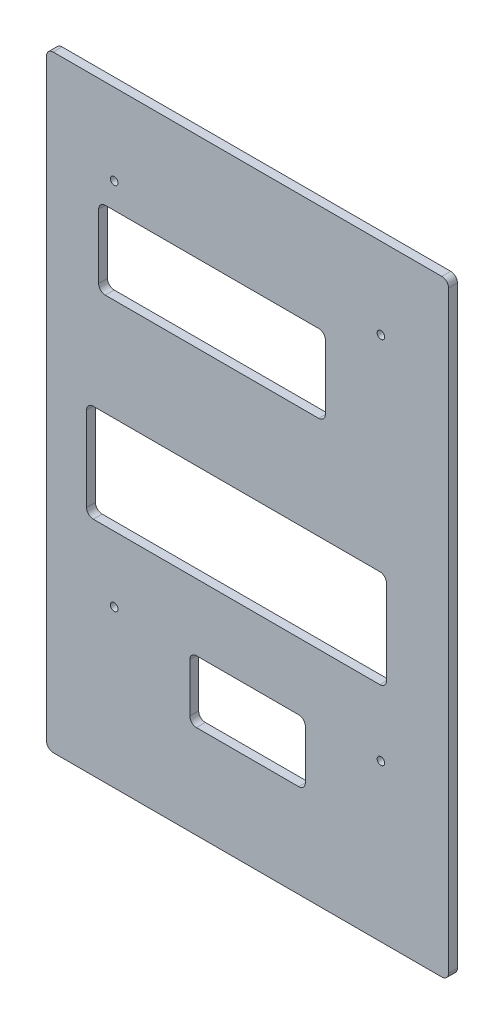
SolidWorks part; units mm, degrees
material "Verre"
ref_plane "Plan de face" through (0, 0, 0) normal (0, 0, 1) x (1, 0, 0)
ref_plane "Plan de dessus" through (0, 0, 0) normal (0, 1, 0) x (1, 0, 0)
ref_plane "Plan de droite" through (0, 0, 0) normal (1, 0, 0) x (0, 0, -1)
sketch "Esquisse1" plane through (0, 0, 0) normal (0, 0, 1) x (1, 0, 0)
  line L1 (0, 0) -> (180.86, 0)
  line L2 (0, 0) -> (0, 273)
  line L3 (0, 273) -> (180.86, 273)
  line L4 (180.86, 0) -> (180.86, 273)
  line L5 (64.43, 70) -> (116.43, 70)
  line L6 (64.43, 70) -> (64.43, 42)
  line L7 (64.43, 42) -> (116.43, 42)
  line L8 (116.43, 70) -> (116.43, 42)
  line L9 (18, 144) -> (152.93, 144)
  line L10 (18, 144) -> (18, 100)
  line L11 (18, 100) -> (152.93, 100)
  line L12 (152.93, 144) -> (152.93, 100)
  line L13 (23.43, 225) -> (125.43, 225)
  line L14 (23.43, 225) -> (23.43, 190)
  line L15 (23.43, 190) -> (125.43, 190)
  line L16 (125.43, 225) -> (125.43, 190)
  circle A0 centre (30.43, 236.5) radius 1.5
  circle A1 centre (150.43, 236.5) radius 1.5
  circle A2 centre (30.43, 70.5) radius 1.5
  circle A3 centre (150.43, 70.5) radius 1.5
  dimension "D5" = 3
  dimension "D8" = 3
  dimension "D13" = 3
  dimension "D14" = 3
  dimension "D1" = 180.86
  dimension "D2" = 273
  dimension "D3" = 30.43
  dimension "D4" = 36.5
  dimension "D6" = 36.5
  dimension "D7" = 30.43
  dimension "D9" = 30.43
  dimension "D10" = 30.43
  dimension "D11" = 70.5
  dimension "D12" = 70.5
  dimension "D16" = 42
  dimension "D17" = 28
  dimension "D18" = 30
  dimension "D19" = 44
  dimension "D20" = 52
  dimension "D21" = 18
  dimension "D22" = 27.93
  dimension "D23" = 48
  dimension "D24" = 35
  dimension "D26" = 102
  dimension "D25" = 55.43
  dimension "D15" = 64.43
extrude "Boss.-Extru.1" add sketch "Esquisse1" along normal blind 4
hole_wizard "Dégagement M31" positions "Esquisse2" profile "Esquisse3" hole size "M3" standard "ISO" end condition through all
sketch "Esquisse2" plane through (0, 0, 4) normal (0, 0, 1) x (1, 0, 0)
  point P0 (30.43, 236.5)
  point P3 (150.43, 236.5)
  point P6 (150.43, 70.5)
  point P9 (30.43, 70.5)
sketch "Esquisse3" plane through (30.43, 236.5, 4) normal (1, 0, 0) x (0, -1, 0)
  line L0 (0, 0) -> (0, 4)
  line L1 (0, 4) -> (1.7, 4)
  line L2 (1.7, 4) -> (1.7, 0)
  line L5 (1.7, 0) -> (0, 0)
  line L11 (0, -6.35) -> (0, 107.95) construction
  dimension "Diamètre du perçage jusqu'au prochain" = 3.4
  dimension "Profondeur du perçage jusqu'au prochain" = 4
fillet "Congé1" radius 3 16 edges at (0, 0, 2) (180.86, 0, 2) (116.43, 42, 2) (64.43, 42, 2) (116.43, 70, 2) (64.43, 70, 2) (152.93, 100, 2) (18, 100, 2) (152.93, 144, 2) (18, 144, 2) (180.86, 273, 2) (0, 273, 2) (125.43, 190, 2) (125.43, 225, 2) (23.43, 225, 2) (23.43, 190, 2)
sketch "Esquisse4" [suppressed] plane through (0, 0, 4) normal (0, 0, 1) x (1, 0, 0)
  line L0 (27.93, 165) -> (162.86, 165) construction
  line L1 (58.43, 190) -> (154.43, 190) construction
  line L3 (27.93, 165) -> (27.93, 135.3531) construction
  line L4 (162.86, 165) -> (162.86, 135.3531) construction
  line L5 (27.93, 141) -> (27.93, 103) construction
  line L6 (162.86, 103) -> (162.86, 141) construction
  dimension "D1" = 25
sketch "Esquisse5" plane through (0, 0, 0) normal (0, 0, -1) x (-1, 0, 0)
  line L0 (-56.9089, 202.3439) -> (421.0911, 202.3439) construction
  line L1 (107.0911, 240.8566) -> (1241.0911, 240.8566) construction
  line L2 (-94.2833, 174.0347) -> (-91.1852, 174.0347)
  line L3 (-91.1852, 174.0347) -> (-91.1824, 166.7906)
  line L4 (-84.6968, 170.3369) -> (-88.3318, 166.2594)
  line L5 (-88.3318, 166.2594) -> (-84.4535, 160.0184)
  line L6 (-84.4535, 160.0184) -> (-87.9228, 160.0184)
  line L7 (-87.9228, 160.0184) -> (-90.4278, 164.3432)
  line L8 (-91.1824, 160.0184) -> (-94.2833, 160.0184)
  line L9 (-94.2833, 160.0184) -> (-94.2833, 174.0347)
  line L10 (-78.7925, 174.0347) -> (-75.6893, 174.0347)
  line L11 (-75.6893, 174.0347) -> (-75.6893, 169.1495)
  line L12 (-69.5264, 160.0184) -> (-72.6249, 160.0184)
  line L13 (-75.6943, 160.0184) -> (-78.7925, 160.0184)
  line L14 (-78.7925, 160.0184) -> (-78.7925, 174.0347)
  line L15 (-139.2569, 172.9353) -> (-137.1581, 172.9353)
  line L16 (-137.1581, 172.9353) -> (-137.1581, 170.4368)
  line L17 (-137.1581, 170.4368) -> (-133.6735, 170.4368)
  line L18 (-133.6735, 170.4368) -> (-133.6735, 168.1381)
  line L19 (-133.6735, 168.1381) -> (-137.1581, 168.1381)
  line L20 (-137.1581, 168.1381) -> (-137.1581, 162.8704)
  line L21 (-133.2794, 162.5414) -> (-133.2794, 160.2428)
  line L22 (-140.1754, 168.1381) -> (-141.7532, 168.1381)
  line L23 (-141.7532, 168.1381) -> (-141.7532, 170.3369)
  line L24 (-141.7532, 170.3369) -> (-140.0239, 170.3369)
  line L25 (-140.0239, 170.3369) -> (-139.2569, 172.9353)
  line L26 (-12.9312, 172.9353) -> (-10.9324, 172.8354)
  line L27 (-10.9324, 172.8354) -> (-10.8324, 170.4368)
  line L28 (-10.8324, 170.4368) -> (-7.4344, 170.4368)
  line L29 (-7.4344, 170.4368) -> (-7.4344, 168.1381)
  line L30 (-7.4344, 168.1381) -> (-10.9324, 168.1381)
  line L31 (-10.9324, 168.1381) -> (-10.8324, 162.5414)
  line L32 (-57.505, 164.5403) -> (-59.1422, 164.5403)
  line L33 (-7.0347, 162.4415) -> (-7.0347, 160.2428)
  line L34 (-13.8145, 168.2381) -> (-15.4406, 168.2381)
  line L35 (-15.4406, 168.2381) -> (-15.4406, 170.4368)
  line L36 (-15.4406, 170.4368) -> (-13.7165, 170.4368)
  line L37 (-13.7165, 170.4368) -> (-12.9312, 172.9353)
  line L38 (-174.2363, 172.8354) -> (-163.6381, 172.8354)
  line L39 (-163.6381, 172.8354) -> (-163.6381, 170.2335)
  line L40 (-163.6381, 170.2335) -> (-167.3327, 170.2335)
  line L41 (-167.3327, 170.2335) -> (-167.3327, 160.0184)
  line L42 (-167.3327, 160.0184) -> (-170.5222, 160.0184)
  line L43 (-170.5222, 160.0184) -> (-170.5703, 170.2335)
  line L44 (-170.5703, 170.2335) -> (-174.2363, 170.2335)
  line L45 (-174.2363, 170.2335) -> (-174.2363, 172.8354)
  line L46 (-47.2135, 160.0661) -> (-47.2135, 172.8354)
  line L47 (-27.5226, 172.1358) -> (-25.224, 172.0359)
  line L48 (-25.224, 172.0359) -> (-24.9241, 170.6367)
  line L49 (-22.8254, 171.1364) -> (-21.1497, 169.4374)
  line L50 (-21.6333, 167.3283) -> (-20.2269, 167.1387)
  line L51 (-20.2269, 167.1387) -> (-20.3269, 164.8401)
  line L52 (-20.3269, 164.8401) -> (-21.726, 164.5403)
  line L53 (-21.3263, 162.4415) -> (-22.9253, 160.8424)
  line L54 (-22.9253, 160.8424) -> (-24.1246, 161.642)
  line L55 (-25.0241, 161.2422) -> (-25.3239, 159.843)
  line L56 (-25.3239, 159.843) -> (-27.5226, 159.943)
  line L57 (-27.5226, 159.943) -> (-27.8224, 161.3421)
  line L58 (-29.9212, 160.9424) -> (-31.5203, 162.5414)
  line L59 (-31.5203, 162.5414) -> (-30.7207, 163.7407)
  line L60 (-31.1205, 164.6402) -> (-32.5197, 164.94)
  line L61 (-32.5197, 164.94) -> (-32.4197, 167.1387)
  line L62 (-32.4197, 167.1387) -> (-31.0206, 167.4386)
  line L63 (-30.7207, 168.338) -> (-31.5203, 169.5373)
  line L64 (-31.5203, 169.5373) -> (-29.9212, 171.0364)
  line L65 (-27.8224, 170.6367) -> (-27.5226, 172.1358)
  line L66 (-121.3674, 171.736) -> (-113.2722, 160.1428)
  line L67 (-113.2722, 160.1428) -> (-130.1622, 160.2428)
  line L68 (-130.1622, 160.2428) -> (-121.3674, 171.736)
  line L69 (-101.122, 160.0184) -> (-104.166, 160.0184)
  line L70 (-107.2724, 160.0184) -> (-110.3739, 160.0184)
  line L71 (-110.3739, 160.0184) -> (-110.3739, 170.4368)
  line L72 (-110.3739, 170.4368) -> (-107.471, 170.4368)
  line L73 (-107.2724, 169.1495) -> (-107.471, 169.1495)
  line L74 (-55.5361, 159.943) -> (-54.06, 159.943)
  line L75 (-53.0008, 162.1272) -> (-53.0008, 160.2428)
  line L76 (-57.4815, 166.5394) -> (-57.4815, 167.3283)
  line L77 (-59.7101, 167.0388) -> (-62.9094, 167.1387)
  line L78 (-157.7434, 170.3369) -> (-154.6917, 170.352)
  line L79 (-151.8049, 170.352) -> (-148.7513, 170.3369)
  line L80 (-148.7513, 170.3369) -> (-148.6473, 160.0184)
  line L81 (-148.6473, 160.0184) -> (-151.6216, 160.0184)
  line L82 (-151.6216, 160.0184) -> (-151.6216, 161.4269)
  line L83 (-122.8785, 167.7334) -> (-124.9653, 161.2422)
  line L84 (-124.9653, 161.2422) -> (-127.9635, 161.3421)
  line L85 (-127.9635, 161.3421) -> (-122.8785, 167.7334)
  line L86 (-121.2675, 169.4374) -> (-115.4709, 161.3421)
  line L87 (-115.4709, 161.3421) -> (-123.6661, 161.3421)
  line L88 (-123.6661, 161.3421) -> (-121.2675, 169.4374)
  line L89 (-44.0087, 167.9383) -> (-44.0087, 170.3369)
  line L90 (-44.0267, 165.4648) -> (-44.0267, 162.5414)
  line L91 (-44.0267, 162.5414) -> (-41.8105, 162.5414)
  line L92 (-41.8105, 165.4648) -> (-44.0267, 165.4648)
  line L93 (-22.0456, 168.2381) -> (-21.1497, 169.4374)
  line L94 (-22.0456, 168.2381) -> (-21.6333, 167.3283)
  line L95 (-25.0241, 161.2422) -> (-24.1246, 161.642)
  line L96 (-31.1205, 164.6402) -> (-30.7207, 163.7407)
  line L97 (-30.7207, 168.338) -> (-31.0206, 167.4386)
  line L98 (-60.0892, 163.7407) -> (-60.0892, 162.8704)
  line L99 (-57.505, 164.5403) -> (-57.505, 163.8272)
  line L100 (-154.6917, 170.352) -> (-154.6917, 164.3054)
  line L101 (-151.8049, 170.352) -> (-151.8049, 164.3054)
  line L102 (-107.471, 169.1495) -> (-107.471, 170.4368)
  line L103 (-101.122, 160.0184) -> (-101.122, 167.4386)
  line L104 (-104.166, 160.0184) -> (-104.166, 165.9507)
  line L105 (-107.2724, 160.0184) -> (-107.2724, 165.9507)
  line L106 (-84.6968, 170.3369) -> (-88.0776, 170.3369)
  line L107 (-88.0776, 170.3369) -> (-91.1824, 166.7906)
  line L108 (-91.1824, 160.0184) -> (-91.1824, 163.8272)
  line L109 (-91.1824, 163.8272) -> (-90.4278, 164.3432)
  line L110 (-75.6943, 160.0184) -> (-75.6943, 165.9507)
  line L111 (-72.6249, 160.0184) -> (-72.6249, 166.7906)
  line L112 (-69.5264, 160.0184) -> (-69.5264, 167.4386)
  line L113 (-54.4145, 167.0061) -> (-54.4145, 162.6507)
  line L114 (-47.2135, 172.8354) -> (-41.5192, 172.8354)
  line L115 (-47.2135, 160.0661) -> (-40.67, 160.0661)
  line L116 (-44.0087, 170.3369) -> (-42.1743, 170.3369)
  line L117 (-44.0087, 167.9383) -> (-42.0498, 167.9383)
  arc A0 (-59.1422, 164.5403) -> (-60.0892, 163.7407) centre (-59.1422, 163.5797) ccw
  circle A1 centre (-26.3868, 165.9832) radius 2.3707
  arc A2 (-41.8105, 162.5414) -> (-41.8105, 165.4648) centre (-41.8105, 164.0031) ccw
  spline S0 degree 3 poles (-75.6943, 165.9507) (-75.607, 166.6089) (-75.1986, 167.568) (-73.6088, 168.4964) (-72.5255, 167.5211) (-72.6249, 166.7906) knots 0 0 0 0 0.394541 0.59607 1 1 1 1
  spline S1 degree 3 poles (-75.6893, 169.1495) (-75.2594, 169.7597) (-73.9101, 170.5281) (-70.9079, 170.7231) (-69.5421, 168.6416) (-69.5264, 167.4386) knots 0 0 0 0 0.262741 0.558365 1 1 1 1
  spline S2 degree 3 poles (-54.4145, 162.6507) (-54.3978, 162.4449) (-54.1312, 161.7319) (-53.3221, 162.0376) (-53.0008, 162.1272) knots 0 0 0 0 0.373122 1 1 1 1
  spline S3 degree 3 poles (-57.0864, 161.3421) (-56.9419, 160.6025) (-56.2449, 160.0799) (-55.5361, 159.943) knots 0 0 0 0 1 1 1 1
  spline S4 degree 3 poles (-137.1581, 162.8704) (-137.1357, 162.6205) (-136.8298, 162.3293) (-135.4596, 161.9489) (-134.2298, 162.3066) (-133.2794, 162.5414) knots 0 0 0 0 0.163675 0.27749 1 1 1 1
  spline S5 degree 3 poles (-133.2794, 160.2428) (-134.8141, 160.051) (-138.7019, 159.2323) (-139.6757, 161.3421) (-139.8081, 161.6291) (-139.9498, 161.9266) (-139.9755, 162.2416) (-140.1355, 164.2017) (-140.072, 166.1742) (-140.1754, 168.1381) knots 0 0 0 0 1 1 1 2 2 2 3 3 3 3
  spline S6 degree 3 poles (-7.0347, 160.2428) (-8.6244, 160.0676) (-12.4699, 159.3084) (-13.4142, 161.4355) (-13.624, 161.9082) (-13.782, 162.4232) (-13.792, 162.9403) (-13.826, 164.7059) (-13.807, 166.4722) (-13.8145, 168.2381) knots 0 0 0 0 1 1 1 2 2 2 3 3 3 3
  spline S7 degree 3 poles (-40.67, 160.0661) (-39.7367, 160.1577) (-38.4804, 160.8468) (-37.2595, 162.3426) (-37.1701, 163.6675) (-37.1743, 165.538) (-38.7166, 166.4794) (-39.5286, 166.7906) knots 0 0 0 0 0.282707 0.43558 0.571416 0.685536 1 1 1 1
  spline S8 degree 3 poles (-39.5286, 166.7906) (-38.9565, 166.948) (-38.2374, 167.6832) (-37.8968, 168.9733) (-37.8113, 170.1278) (-38.2848, 171.2576) (-39.48, 172.3911) (-40.6921, 172.7767) (-41.5192, 172.8354) knots 0 0 0 0 0.199158 0.317575 0.451003 0.584991 0.71822 1 1 1 1
  spline S9 degree 3 poles (-24.9241, 170.6367) (-23.5477, 170.1779) (-23.8936, 170.4242) (-22.8254, 171.1364) knots 0 0 0 0 1 1 1 1
  spline S10 degree 3 poles (-21.726, 164.5403) (-22.2066, 163.0985) (-21.9033, 163.5956) (-21.3263, 162.4415) knots 0 0 0 0 1 1 1 1
  spline S11 degree 3 poles (-27.8224, 161.3421) (-28.7992, 161.6677) (-28.5552, 161.7587) (-29.2216, 161.3421) (-29.4494, 161.1998) (-29.688, 161.0756) (-29.9212, 160.9424) knots 0 0 0 0 1 1 1 2 2 2 2
  spline S12 degree 3 poles (-29.9212, 171.0364) (-29.4943, 170.8941) (-29.1686, 170.3865) (-28.7219, 170.3369) (-28.3801, 170.2989) (-28.1209, 170.5372) (-27.8224, 170.6367) knots 0 0 0 0 1 1 1 2 2 2 2
  spline S13 degree 3 poles (-107.2724, 169.1495) (-106.8585, 169.8299) (-105.5179, 170.598) (-103.5202, 170.6358) (-101.6572, 169.6874) (-101.1521, 168.2861) (-101.122, 167.4386) knots 0 0 0 0 0.27864 0.525252 0.687769 1 1 1 1
  spline S14 degree 3 poles (-107.2724, 165.9507) (-107.2465, 166.745) (-106.2762, 168.5882) (-104.0431, 167.7417) (-104.2041, 166.4557) (-104.166, 165.9507) knots 0 0 0 0 0.496685 0.694227 1 1 1 1
  spline S15 degree 2 poles (-54.06, 159.943) (-53.5081, 160.0158) (-53.0008, 160.2428) knots 0 0 0 1 1 1
  spline S16 degree 3 poles (-59.7101, 167.0388) (-59.773, 167.4531) (-59.3518, 168.8785) (-57.4745, 168.3639) (-57.4815, 167.3283) knots 0 0 0 0 0.367002 1 1 1 1
  spline S17 degree 3 poles (-57.0864, 161.3421) (-57.3774, 161.0516) (-57.8191, 160.5577) (-58.1867, 160.3437) (-59.3607, 159.6603) (-61.068, 159.6271) (-62.1842, 160.4472) (-63.7018, 161.5622) (-63.6714, 164.6228) (-62.0796, 165.6441) (-60.7256, 166.5129) (-59.0024, 166.4238) (-57.4815, 166.5394) knots 0 0 0 0 1 1 1 2 2 2 3 3 3 4 4 4 4
  spline S18 degree 3 poles (-62.9094, 167.1387) (-62.8636, 167.8511) (-62.16, 169.9427) (-59.8154, 170.6023) (-58.5702, 170.5768) knots 0 0 0 0 0.353066 1 1 1 1
  spline S19 degree 3 poles (-154.6917, 164.3054) (-154.7394, 163.7332) (-154.5444, 163.0059) (-153.7633, 162.1776) (-152.8735, 162.3733) (-152.0344, 163.0441) (-151.8568, 163.8566) (-151.8049, 164.3054) knots 0 0 0 0 0.303187 0.415254 0.583999 0.737935 1 1 1 1
  spline S20 degree 3 poles (-151.6216, 161.4269) (-151.9172, 161.1229) (-152.1728, 160.7741) (-152.5084, 160.515) (-152.7443, 160.3329) (-153.0209, 160.2022) (-153.3023, 160.1041) (-155.6394, 159.2885) (-157.5509, 160.7972) (-157.6441, 163.2417) (-157.7341, 165.6053) (-157.7103, 167.9718) (-157.7434, 170.3369) knots 0 0 0 0 1 1 1 2 2 2 3 3 3 4 4 4 4
  spline S21 degree 3 poles (-42.0498, 167.9383) (-41.6698, 167.9271) (-41.2486, 168.3464) (-41.0744, 169.1173) (-41.2166, 169.9639) (-41.8255, 170.2992) (-42.1743, 170.3369) knots 0 0 0 0 0.294875 0.472372 0.68529 1 1 1 1
  spline S23 degree 3 poles (-7.0347, 162.4415) (-7.8006, 162.2378) (-9.0559, 162.1282) (-10.4545, 162.0729) (-10.8324, 162.5414) knots 0 0 0 0 0.590902 1 1 1 1
  spline S24 degree 3 poles (-57.505, 163.8272) (-57.5306, 163.3193) (-57.9984, 162.5511) (-59.1839, 162.1257) (-60.0621, 162.2684) (-60.0892, 162.8704) knots 0 0 0 0 0.406447 0.637072 1 1 1 1
  spline S25 degree 3 poles (-54.4145, 167.0061) (-54.3865, 167.6214) (-54.6519, 168.6026) (-55.5308, 169.6381) (-56.7202, 170.5068) (-57.8839, 170.5371) (-58.5702, 170.5768) knots 0 0 0 0 0.300061 0.46914 0.655769 1 1 1 1
ref_plane "Plan1" [suppressed] through (0, 0, 2) normal (0, 0, 1) x (1, 0, 0)
extrude "Enlèv. mat.-Extru.2" cut sketch "Esquisse5" against normal blind 1
equation "\"D7@Esquisse1\"=\"D3@Esquisse1\""
equation "\"D9@Esquisse1\"=\"D3@Esquisse1\""
equation "\"D10@Esquisse1\"=\"D3@Esquisse1\""
equation "\"D12@Esquisse1\"=\"D11@Esquisse1\""
equation "\"D13@Esquisse1\"=\"D5@Esquisse1\""
equation "\"D14@Esquisse1\"=\"D8@Esquisse1\""
